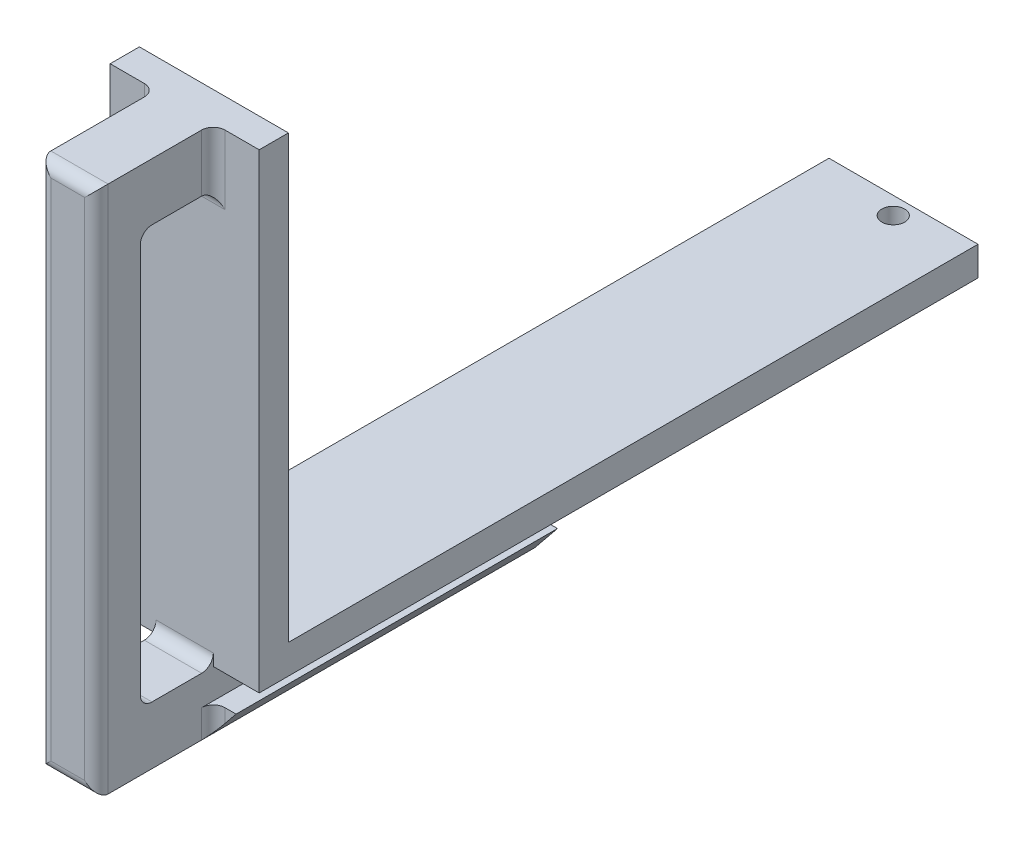
SolidWorks part; units mm, degrees
note: The reader was unsure of these and kept them because the rebuilt part matched: shared geometry of "Sketch5<4>".
ref_plane "Front Plane" through (0, 0, 0) normal (0, 0, 1) x (1, 0, 0)
ref_plane "Top Plane" through (0, 0, 0) normal (0, 1, 0) x (1, 0, 0)
ref_plane "Right Plane" through (0, 0, 0) normal (1, 0, 0) x (0, 0, -1)
sketch "Sketch1" plane through (0, 0, 0) normal (0, 1, 0) x (1, 0, 0)
  line L1 (-12.75, -59) -> (12.75, -59)
  line L2 (-12.75, -59) -> (-12.75, 59)
  line L3 (-12.75, 59) -> (12.75, 59)
  line L4 (12.75, -59) -> (12.75, 59)
  line L5 (-12.75, -59) -> (12.75, 59) construction
  line L6 (-12.75, 59) -> (12.75, -59) construction
  point P0 (0, 0)
  dimension "D1" = 118
  dimension "D2" = 25.5
extrude "Boss-Extrude1" add sketch "Sketch1" along normal blind 5
sketch "Sketch2" plane through (0, 5, 0) normal (0, 1, 0) x (1, 0, 0)
  line L0 (12.75, 0) -> (-12.75, 0) construction
  line L1 (12.75, -59) -> (12.75, 59) construction
  line L2 (-12.75, 59) -> (-12.75, -59) construction
  circle A0 centre (1.25, 56) radius 1.95
  circle A1 centre (1.25, -56) radius 1.95
  dimension "D1" = 3.9
  dimension "D2" = 112
  dimension "D3" = 14
sketch "Sketch5" plane through (0, 0, 59) normal (0, 0, 1) x (1, 0, 0)
  line L1 (-12.75, 0) -> (12.75, 0) construction
  line L2 (-4.9, 0) -> (-4.9, -5.1)
  line L4 (-4.9, -9.9) -> (4.9, -9.9)
  line L6 (4.9, -5.1) -> (4.9, 0)
  line L7 (4.9, 0) -> (-4.9, 0)
  line L8 (0, 0) -> (0, -9.9) construction
  line L9 (-4.9, -5.1) -> (-8.8, -5.1)
  line L10 (-8.8, -5.1) -> (-4.9, -9.9)
  line L11 (4.9, -5.1) -> (8.8, -5.1)
  line L12 (8.8, -5.1) -> (4.9, -9.9)
  dimension "D1" = 5.1
  dimension "D2" = 4.8
  dimension "D3" = 3.9
  dimension "D4" = 9.8
extrude "Boss-Extrude5" add sketch "Sketch5" along direction (0, 0, -1) on the side against the normal blind 50
extrude "Cut-Extrude1" cut sketch "Sketch2" against normal blind 10
extrude "Boss-Extrude7" add sketch "Sketch5<4>" along normal blind 5
sketch "Sketch5<4>" plane through (0, 0, 59) normal (0, 0, 1) x (1, 0, 0) same geometry as "Sketch5"
sketch "Sketch8" plane through (0, 0, 0) normal (0, 1, 0) x (1, 0, 0)
  line L0 (4.9, -64) -> (-4.9, -64) construction
  line L1 (-4.9, -64) -> (12.75, -64)
  line L3 (-4.9, -59) -> (12.75, -59)
  line L4 (12.75, -64) -> (12.75, -59)
  line L5 (-4.9, -9) -> (-4.9, -64) construction
  line L6 (-4.9, -59) -> (-12.75, -59)
  line L11 (-12.75, -59) -> (-12.75, -64)
  line L12 (-12.75, -64) -> (-4.9, -64)
extrude "Boss-Extrude8" add sketch "Sketch8" along normal blind 80.5
sketch "Sketch9" plane through (0, 0, 64) normal (0, 0, 1) x (1, 0, 0)
  line L0 (0, 80.5) -> (0, -9.9) construction
  line L1 (-12.75, 80.5) -> (12.75, 80.5) construction
  line L2 (-4.9, -9.9) -> (4.9, -9.9) construction
  line L4 (-4.9, 70.7) -> (4.9, 70.7)
  line L5 (-4.9, 70.7) -> (-4.9, 80.5)
  line L6 (-4.9, 80.5) -> (4.9, 80.5)
  line L7 (4.9, 70.7) -> (4.9, 80.5)
  line L8 (-4.9, 70.7) -> (4.9, 80.5) construction
  line L9 (-4.9, 80.5) -> (4.9, 70.7) construction
  line L10 (-4.9, -9.9) -> (4.9, -9.9)
  line L11 (-4.9, -9.9) -> (-4.9, 0)
  line L12 (-4.9, 0) -> (4.9, 0)
  line L13 (4.9, -9.9) -> (4.9, 0)
  line L14 (-4.9, -9.9) -> (4.9, 0) construction
  line L15 (-4.9, 0) -> (4.9, -9.9) construction
  line L17 (-12.75, 0) -> (-4.9, 0) construction
  point P6 (0, 75.6)
  point P11 (0, -4.95)
  point P16 (0, 68.5347)
  point P17 (0, 5.0099)
  point P18 (0, 0)
  point P19 (0, 10.188)
  point P20 (0, -4.4728)
  dimension "D1" = 9.8
extrude "Boss-Extrude10" add sketch "Sketch9" along normal blind 12.5
sketch "Sketch10" plane through (0, 0, 76.5) normal (0, 0, 1) x (1, 0, 0)
  line L0 (4.9, 80.5) -> (4.9, -9.9)
  line L1 (-4.9, 80.5) -> (4.9, 80.5)
  line L5 (4.9, -9.9) -> (-4.9, -9.9)
  line L6 (-4.9, -9.9) -> (-4.9, 80.5)
extrude "Boss-Extrude11" add sketch "Sketch10" along normal blind 7.5
fillet "Fillet1" radius 2 8 edges at (0, 0, 64) (0, 0, 76.5) (-4.9, 35.3, 84) (0, -9.9, 84) (4.9, 35.3, 84) (0, 80.5, 84) (0, 70.7, 64) (0, 70.7, 76.5)
